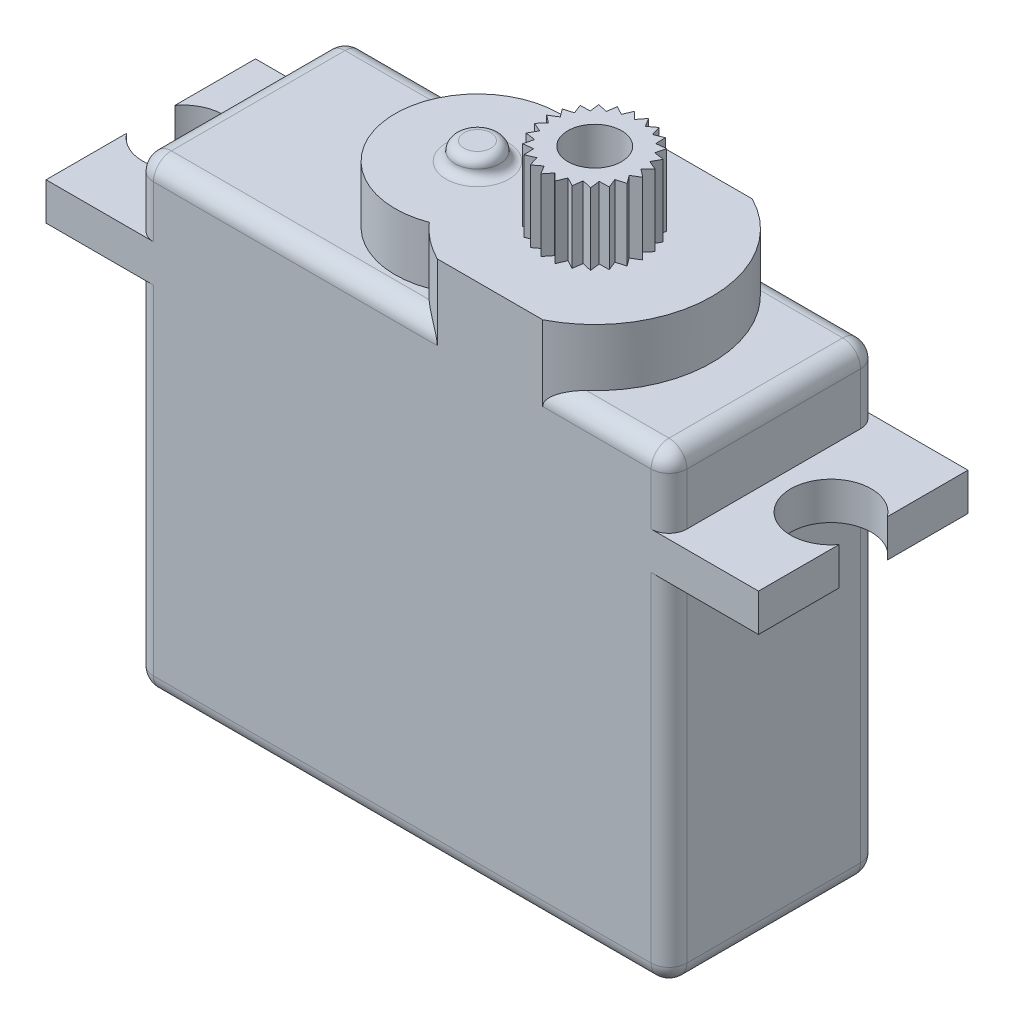
SolidWorks part; units mm, degrees
ref_plane "Front Plane" through (0, 0, 0) normal (0, 0, 1) x (1, 0, 0)
ref_plane "Top Plane" through (0, 0, 0) normal (0, 1, 0) x (1, 0, 0)
ref_plane "Right Plane" through (0, 0, 0) normal (1, 0, 0) x (0, 0, -1)
sketch "Sketch1" plane through (0, 0, 0) normal (0, 0, 1) x (1, 0, 0)
  line L0 (0, 12.95) -> (0, -12.95) construction
  line L1 (-14.9, 0) -> (14.9, 0) construction
  line L2 (-14.9, -12.95) -> (-14.9, 6.95)
  line L3 (-14.9, -12.95) -> (14.9, -12.95)
  line L4 (-14.9, 9.05) -> (-14.9, 12.95)
  line L5 (14.9, 12.95) -> (-14.9, 12.95)
  line L6 (-14.9, 9.05) -> (-19.9, 9.05)
  line L7 (-19.9, 9.05) -> (-19.9, 6.95)
  line L8 (-19.9, 6.95) -> (-14.9, 6.95)
  line L9 (14.9, 9.05) -> (19.9, 9.05)
  line L10 (19.9, 9.05) -> (19.9, 6.95)
  line L11 (19.9, 6.95) -> (14.9, 6.95)
  line L12 (14.9, 12.95) -> (14.9, 9.05)
  line L13 (14.9, 6.95) -> (14.9, -12.95)
  point P4 (0, 0)
  point P8 (0, 12.95)
  point P11 (0, -12.95)
  dimension "D1" = 25.9
  dimension "D2" = 29.8
  dimension "D3" = 2.1
  dimension "D4" = 19.9
  dimension "D5" = 5
extrude "Extrude1" add sketch "Sketch1" along normal mid plane 11.7
sketch "Sketch2" plane through (0, 0, 0) normal (0, 1, 0) x (1, 0, 0)
  line L0 (-18.1, 0) -> (18.1, 0) construction
  circle A0 centre (-18.1, 0) radius 2.25
  circle A1 centre (18.1, 0) radius 2.25
  point P2 (0, 0)
  dimension "D2" = 4.5
  dimension "D1" = 36.2
extrude "Extrude2" cut sketch "Sketch2" against normal up to surface (2.1 mm away) from vertex at 9.05 up to face at (-17.4, 6.95, 0) starting at point (-19.9, 9.05, 5.85)
sketch "Sketch3" plane through (0, 0, 0) normal (0, 1, 0) x (1, 0, 0)
  line L0 (14.9, 0) -> (4.9, 0) construction
  line L1 (14.9, -5.85) -> (14.9, 5.85) construction
  line L2 (14.9, -5.85) -> (14.9, 5.85) construction
  line L3 (-6.25, 0) -> (11.45, 0) construction
  line L4 (1.9538, 5.85) -> (7.8462, 5.85)
  line L5 (1.9538, -5.85) -> (7.8462, -5.85)
  line L6 (14.9, -5.85) -> (-14.9, -5.85) construction
  line L7 (14.9, 5.85) -> (-14.9, 5.85) construction
  circle A0 centre (4.9, 0) radius 6.55
  circle A1 centre (-1.65, 0) radius 4.6
  dimension "D3" = 9.2
  dimension "D1" = 10
  dimension "D2" = 17.7
extrude "Extrude3" add sketch "Sketch3" along normal blind 3.2 from surface at 12.95 contours A0 A1 | A0 A1 | A1 A0 L5 L4
sketch "Sketch6" plane through (0, 0, 0) normal (0, 1, 0) x (1, 0, 0)
  circle A0 centre (-1.65, 0) radius 1.25
  dimension "D1" = 2.5
extrude "Extrude6" add sketch "Sketch6" along normal blind 1 from surface at 16.15 starting at face at (2.7949, 16.15, 0)
sketch "Sketch4" plane through (0, 0, 0) normal (0, 1, 0) x (1, 0, 0)
  circle A0 centre (4.9, 0) radius 2.85
  circle A1 centre (4.9, 0) radius 1.5
  dimension "D1" = 5.7
  dimension "D2" = 3
extrude "Extrude4" add sketch "Sketch4" along normal blind 4 from surface at 16.15 contours A0 A1 starting at face at (-0.4, 16.15, 0)
sketch "Sketch5" plane through (0, 0, 0) normal (0, 1, 0) x (1, 0, 0)
  line L0 (4.9, 0) -> (4.0051, -2.7058) construction
  line L1 (4.9, 0) -> (4.7359, -2.8453) construction
  line L2 (4.0051, -2.7058) -> (4.4471, -2.3739)
  line L3 (4.4471, -2.3739) -> (4.7359, -2.8453)
  line L4 (4.9, 0) -> (4.4471, -2.3739) construction
  circle A0 centre (4.9, 0) radius 2.85 construction
  arc A1 (4.0051, -2.7058) -> (4.7359, -2.8453) centre (4.9, 0) ccw
  dimension "D1" = 15
extrude "Extrude5" cut sketch "Sketch5" against normal up to surface (4 mm away) from surface at 20.15 contours L2 A1 L3 up to face at (7.75, 16.15, 0) starting at face at (6.4, 20.15, 0)
pattern_circular "CirPattern1" count 24 over 360 about axis through (4.9, 0, 0) along (0, 1, 0) of "Extrude5"
fillet "Fillet1" radius 1 18 edges at (14.9, 12.95, 0) (-14.9, 12.95, 0) (14.9, -12.95, 0) (-14.9, -12.95, 0) (0, -12.95, 5.85) (0, -12.95, -5.85) (14.9, 11, -5.85) (-14.9, 11, -5.85) (-14.9, 11, 5.85) (14.9, 11, 5.85) (14.9, -3, 5.85) (14.9, -3, -5.85) (-14.9, -3, -5.85) (-14.9, -3, 5.85)
fillet "Fillet2" radius 0.5 2 edges at (-0.4, 17.15, 0) (-0.4, 16.15, 0)
